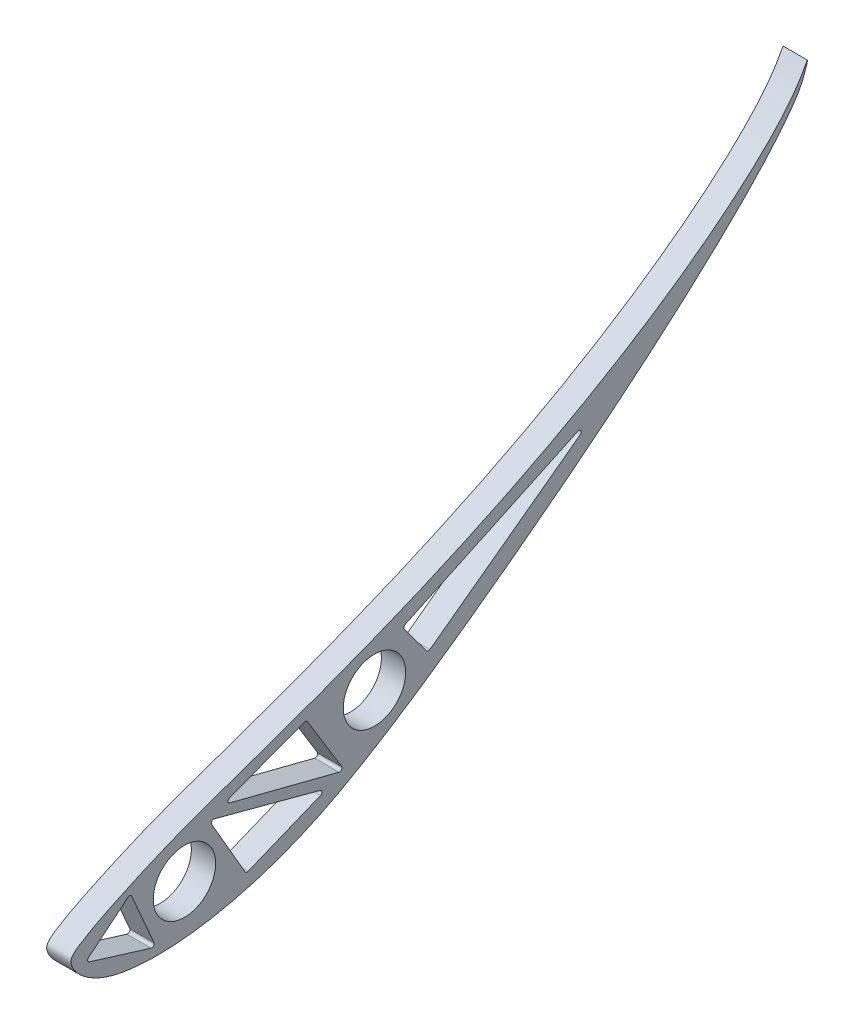
SolidWorks part; units mm, degrees
ref_plane "Front Plane" through (0, 0, 0) normal (0, 0, 1) x (1, 0, 0)
ref_plane "Top Plane" through (0, 0, 0) normal (0, 1, 0) x (1, 0, 0)
ref_plane "Right Plane" through (0, 0, 0) normal (1, 0, 0) x (0, 0, -1)
ref_plane "Plane1" through (-663.1866, 190.6859, 1129.097) normal (0, -0.8863, 0.463) x (-1, 0, 0)
sketch "Sketch2" plane through (-668.2666, 0, 0) normal (-1, 0, 0) x (0, 0, 1)
  line L0 (1168.9542, 157.0649) -> (1171.2656, 160.2017)
  line L1 (1168.5991, 157.0111) -> (1152.8543, 168.6125)
  line L2 (1153.1128, 169.0469) -> (1171.1756, 160.5791)
  line L3 (1177.8308, 151.028) -> (1181.4125, 156.8861)
  line L4 (1181.7181, 156.9915) -> (1189.5577, 154.0625)
  line L5 (1189.5319, 153.5785) -> (1178.1106, 150.6494)
  line L6 (1180.0737, 149.9801) -> (1191.1375, 152.9364)
  line L7 (1191.423, 152.5638) -> (1187.9328, 146.5284)
  line L8 (1187.6173, 146.4203) -> (1180.0436, 149.4994)
  line L9 (1199.8, 150.2493) -> (1197.4664, 144.8773)
  line L10 (1197.774, 144.5333) -> (1204.2277, 146.5168)
  line L11 (1204.3144, 146.9557) -> (1200.1943, 150.3442)
  circle A1 centre (1194.2825, 148.8381) radius 3.2639
  circle A2 centre (1174.3977, 156.2245) radius 3.2639
  arc A3 (1171.2656, 160.2017) -> (1171.1756, 160.5791) centre (1171.0611, 160.3524) ccw
  arc A4 (1168.9542, 157.0649) -> (1168.5991, 157.0111) centre (1168.7498, 157.2155) cw
  arc A5 (1152.8543, 168.6125) -> (1153.1128, 169.0469) centre (1153.005, 168.817) cw
  arc A6 (1177.8308, 151.028) -> (1178.1106, 150.6494) centre (1178.0475, 150.8955) ccw
  arc A7 (1181.4125, 156.8861) -> (1181.7181, 156.9915) centre (1181.6292, 156.7536) cw
  arc A8 (1189.5577, 154.0625) -> (1189.5319, 153.5785) centre (1189.4688, 153.8245) cw
  arc A9 (1180.0737, 149.9801) -> (1180.0436, 149.4994) centre (1180.1392, 149.7347) ccw
  arc A10 (1191.423, 152.5638) -> (1191.1375, 152.9364) centre (1191.2031, 152.691) ccw
  arc A11 (1187.6173, 146.4203) -> (1187.9328, 146.5284) centre (1187.7129, 146.6556) ccw
  arc A12 (1199.8, 150.2493) -> (1200.1943, 150.3442) centre (1200.0329, 150.1481) cw
  arc A13 (1197.774, 144.5333) -> (1197.4664, 144.8773) centre (1197.6994, 144.7761) cw
  arc A14 (1204.2277, 146.5168) -> (1204.3144, 146.9557) centre (1204.153, 146.7596) ccw
  spline S0 degree 3 poles (1129.0253, 190.7743) (1128.8417, 191.2007) (1129.0652, 190.7387) (1129.2798, 190.3487) (1129.8405, 189.3372) (1130.683, 188.1068) (1131.9633, 186.5546) (1133.6279, 184.8315) (1135.6529, 182.95) (1138.0106, 180.9614) (1140.6791, 178.8994) (1143.6274, 176.797) (1146.825, 174.6871) (1150.2335, 172.5953) (1153.8144, 170.5466) (1157.5274, 168.5631) (1161.3292, 166.6608) (1165.1761, 164.8534) (1169.0269, 163.1538) (1172.8369, 161.5643) (1176.5667, 160.0898) (1180.1759, 158.7288) (1183.6283, 157.4779) (1186.8888, 156.3294) (1189.9259, 155.2712) (1192.7185, 154.2977) (1195.2474, 153.3469) (1197.5173, 152.4005) (1199.555, 151.5079) (1201.354, 150.6789) (1202.8946, 149.9201) (1204.1688, 149.2554) (1205.1372, 148.6495) (1205.8391, 148.1961) (1206.2288, 147.6298) (1206.0758, 147.0312) (1205.7758, 146.4554) (1205.265, 145.8648) (1204.5826, 145.2995) (1203.7285, 144.7823) (1202.7149, 144.3291) (1201.5329, 143.977) (1200.1899, 143.7308) (1198.694, 143.5746) (1197.0551, 143.5244) (1195.2865, 143.5858) (1193.4005, 143.7629) (1191.4097, 144.0667) (1189.3263, 144.4949) (1187.1654, 145.0568) (1184.9404, 145.7568) (1182.6673, 146.6182) (1180.345, 147.6404) (1177.9774, 148.8506) (1175.5583, 150.2399) (1173.0657, 151.7602) (1170.52, 153.4166) (1167.9265, 155.1848) (1165.2946, 157.0449) (1162.6354, 158.9714) (1159.9688, 160.9456) (1157.3137, 162.9454) (1154.6945, 164.9603) (1152.1309, 166.9772) (1149.639, 168.9824) (1147.237, 170.9667) (1144.9369, 172.9154) (1142.7546, 174.8185) (1140.7009, 176.6617) (1138.7886, 178.4344) (1137.0291, 180.1256) (1135.4321, 181.7251) (1134.0053, 183.2222) (1132.7568, 184.6088) (1131.6923, 185.8761) (1130.816, 187.0169) (1130.1258, 188.0237) (1129.6308, 188.9371) (1129.3397, 189.7276) (1129.118, 190.4407) (1129.0253, 190.7743) (1128.8417, 191.2007) (1129.0652, 190.7387) knots -0.007483 -0.003649 -0.00098 0 0.001 0.004147 0.009748 0.018044 0.028864 0.041831 0.056714 0.073341 0.091508 0.111022 0.131662 0.153208 0.175433 0.19811 0.221011 0.243906 0.266573 0.28881 0.310405 0.331178 0.350944 0.369556 0.386865 0.402753 0.417196 0.43038 0.442363 0.453032 0.462284 0.470026 0.476177 0.48065 0.483553 0.486421 0.489953 0.494097 0.498851 0.504197 0.510125 0.516691 0.524012 0.532092 0.540898 0.550403 0.560581 0.571396 0.582828 0.59483 0.607347 0.620384 0.633969 0.6482 0.663194 0.678899 0.695227 0.712113 0.729459 0.747143 0.76501 0.782905 0.800688 0.818242 0.835449 0.852212 0.86843 0.884009 0.898855 0.912882 0.926011 0.938167 0.94929 0.959322 0.968217 0.975948 0.982474 0.987905 0.992517 0.996351 0.99902 1 1.001 1.004147 1.009748 only from (1129.097, 190.6859) to (1129.097, 190.5217) construction
  spline S1 degree 3 poles (1129.097, 190.6859) (1129.1481, 190.5881) (1129.3236, 190.2696) (1129.8405, 189.3372) (1130.683, 188.1068) (1131.9633, 186.5546) (1133.6279, 184.8315) (1135.6529, 182.95) (1138.0106, 180.9614) (1140.6791, 178.8994) (1143.6274, 176.797) (1146.825, 174.6871) (1150.2335, 172.5953) (1153.8144, 170.5466) (1157.5274, 168.5631) (1161.3292, 166.6608) (1165.1761, 164.8534) (1169.0269, 163.1538) (1172.8369, 161.5643) (1176.5667, 160.0898) (1180.1759, 158.7288) (1183.6283, 157.4779) (1186.8888, 156.3294) (1189.9259, 155.2712) (1192.7185, 154.2977) (1195.2474, 153.3469) (1197.5173, 152.4005) (1199.555, 151.5079) (1201.354, 150.6789) (1202.8946, 149.9201) (1204.1688, 149.2554) (1205.1372, 148.6495) (1205.8391, 148.1961) (1206.2288, 147.6298) (1206.0758, 147.0312) (1205.7758, 146.4554) (1205.265, 145.8648) (1204.5826, 145.2995) (1203.7285, 144.7823) (1202.7149, 144.3291) (1201.5329, 143.977) (1200.1899, 143.7308) (1198.694, 143.5746) (1197.0551, 143.5244) (1195.2865, 143.5858) (1193.4005, 143.7629) (1191.4097, 144.0667) (1189.3263, 144.4949) (1187.1654, 145.0568) (1184.9404, 145.7568) (1182.6673, 146.6182) (1180.345, 147.6404) (1177.9774, 148.8506) (1175.5583, 150.2399) (1173.0657, 151.7602) (1170.52, 153.4166) (1167.9265, 155.1848) (1165.2946, 157.0449) (1162.6354, 158.9714) (1159.9688, 160.9456) (1157.3137, 162.9454) (1154.6945, 164.9603) (1152.1309, 166.9772) (1149.639, 168.9824) (1147.237, 170.9667) (1144.9369, 172.9154) (1142.7546, 174.8185) (1140.7009, 176.6617) (1138.7886, 178.4344) (1137.0291, 180.1256) (1135.4321, 181.7251) (1134.0053, 183.2222) (1132.7568, 184.6088) (1131.6923, 185.8761) (1130.816, 187.0169) (1130.1258, 188.0237) (1129.6308, 188.9371) (1129.3397, 189.7276) (1129.1648, 190.2903) (1129.1019, 190.5051) (1129.097, 190.5217) knots 0.002333 0.002333 0.002333 0.002333 0.004147 0.009748 0.018044 0.028864 0.041831 0.056714 0.073341 0.091508 0.111022 0.131662 0.153208 0.175433 0.19811 0.221011 0.243906 0.266573 0.28881 0.310405 0.331178 0.350944 0.369556 0.386865 0.402753 0.417196 0.43038 0.442363 0.453032 0.462284 0.470026 0.476177 0.48065 0.483553 0.486421 0.489953 0.494097 0.498851 0.504197 0.510125 0.516691 0.524012 0.532092 0.540898 0.550403 0.560581 0.571396 0.582828 0.59483 0.607347 0.620384 0.633969 0.6482 0.663194 0.678899 0.695227 0.712113 0.729459 0.747143 0.76501 0.782905 0.800688 0.818242 0.835449 0.852212 0.86843 0.884009 0.898855 0.912882 0.926011 0.938167 0.94929 0.959322 0.968217 0.975948 0.982474 0.987905 0.992517 0.996351 0.996676 0.996676 0.996676 0.996676
  line M33 (1129.097, 222.25) -> (1129.097, 22.597)
  dimension "D1" = 0.254
  dimension "D2" = 0.254
  dimension "D3" = 0.254
  dimension "D4" = 0.254
  dimension "D5" = 0.254
  dimension "D6" = 0.254
  dimension "D7" = 0.254
  dimension "D8" = 0.254
  dimension "D9" = 0.254
  dimension "D10" = 0.254
  dimension "D11" = 0.254
  dimension "D12" = 0.254
extrude "Boss-Extrude1" add sketch "Sketch2" along normal blind 2.54 contours S1 A14 L10 A13 L9 A12 L11 A11 L8 A9 L6 A10 L7 A2 A1 L1 A5 L2 A3 L0 A4 L4 A8 L5 A6 L3 A7 M33 region at (-668.2666, 160.5217, 1173.7173)
